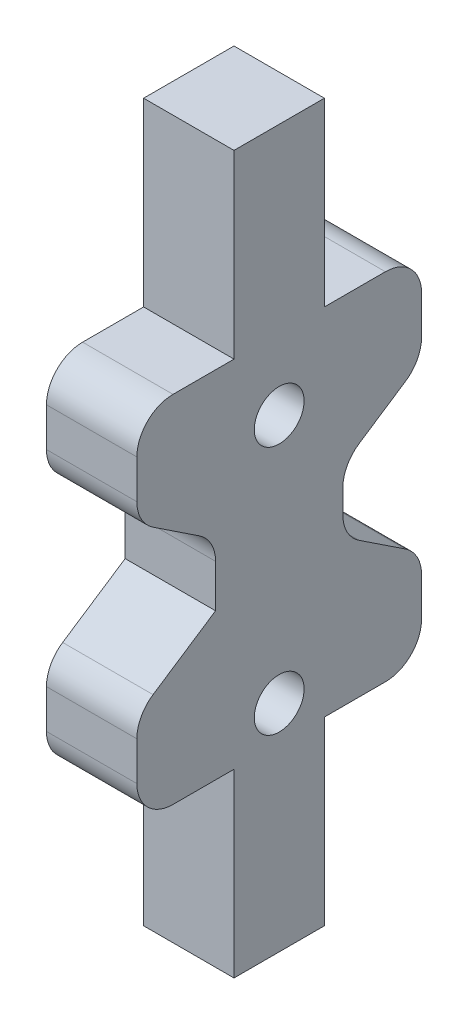
SolidWorks part; units mm, degrees
ref_plane "Front Plane" through (0, 0, 0) normal (0, 0, 1) x (1, 0, 0)
ref_plane "Top Plane" through (0, 0, 0) normal (0, 1, 0) x (1, 0, 0)
ref_plane "Right Plane" through (0, 0, 0) normal (1, 0, 0) x (0, 0, -1)
sketch "Sketch1" plane through (0, 0, 0) normal (1, 0, 0) x (0, 0, -1)
  line L0 (10, 24.952) -> (10, 0) construction
  line L1 (0, 0) -> (6.825, 0)
  line L2 (0, 0) -> (0, 6.6296)
  line L3 (0, 24.952) -> (6.825, 24.952)
  line L4 (20, 0) -> (20, 6.6296)
  line L5 (0, 18.3224) -> (5.5285, 14.6636)
  line L6 (6.825, -12.7) -> (13.175, -12.7)
  line L7 (6.825, -12.7) -> (6.825, 0)
  line L9 (13.175, -12.7) -> (13.175, 0)
  line L10 (6.825, -12.7) -> (13.175, 0) construction
  line L11 (6.825, 0) -> (13.175, -12.7) construction
  line L12 (5.5285, 14.6636) -> (5.5285, 10.2884)
  line L13 (5.5285, 10.2884) -> (0, 6.6296)
  line L14 (0, 18.3224) -> (0, 24.952)
  line L15 (14.4715, 10.2884) -> (20, 6.6296)
  line L16 (14.4715, 14.6636) -> (14.4715, 10.2884)
  line L17 (20, 18.3224) -> (14.4715, 14.6636)
  line L18 (20, 18.3224) -> (20, 24.952)
  line L19 (13.175, 0) -> (20, 0)
  line L20 (14.4715, 12.476) -> (5.5285, 12.476) construction
  line L21 (6.825, 37.652) -> (6.825, 24.952)
  line L22 (6.825, 37.652) -> (13.175, 37.652)
  line L23 (13.175, 37.652) -> (13.175, 24.952)
  line L24 (13.175, 24.952) -> (20, 24.952)
  circle A0 centre (10, 19.952) radius 1.75
  circle A1 centre (10, 2.426) radius 1.75
  point P7 (10, -6.35)
  dimension "D5" = 5
  dimension "D6" = 17.526
  dimension "D1" = 20
  dimension "D2" = 24.952
  dimension "D3" = 12.7
  dimension "D4" = 6.35
extrude "Boss-Extrude1" add sketch "Sketch1" along normal blind 6.35
fillet "Fillet1" radius 2.54 11 edges at (3.175, 14.6636, -14.4715) (3.175, 18.3224, -20) (3.175, 10.2884, -14.4715) (3.175, 6.6296, -20) (3.175, 0, -20) (3.175, 0, 0) (3.175, 6.6296, 0) (3.175, 14.6636, -5.5285) (3.175, 18.3224, 0) (3.175, 24.952, 0) (3.175, 24.952, -20)
